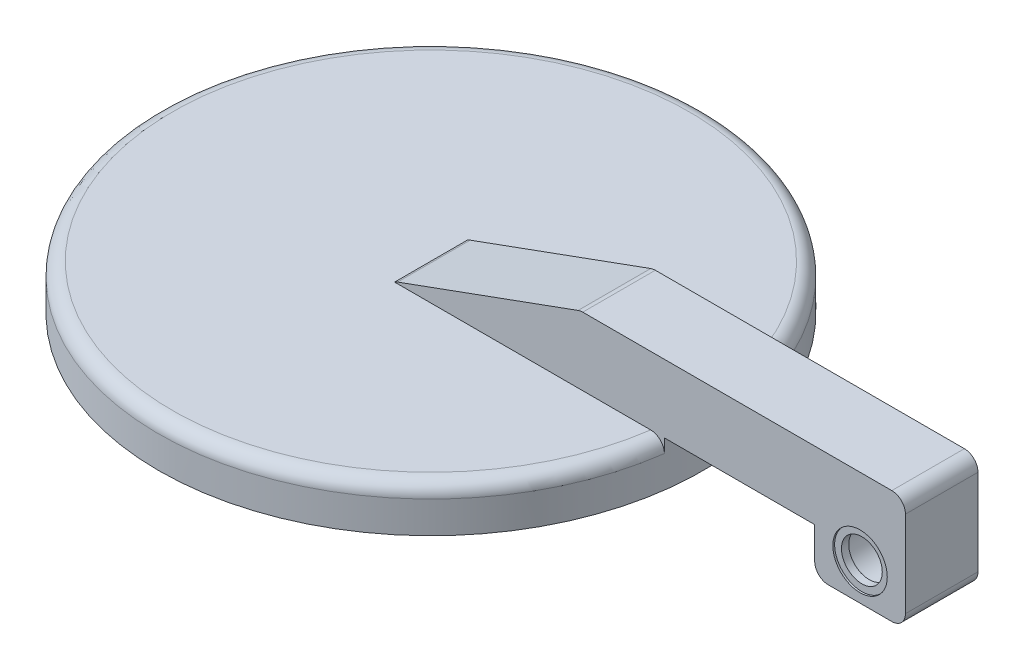
SolidWorks part; units mm, degrees
ref_plane "Front Plane" through (0, 0, 0) normal (0, 0, 1) x (1, 0, 0)
ref_plane "Top Plane" through (0, 0, 0) normal (0, 1, 0) x (1, 0, 0)
ref_plane "Right Plane" through (0, 0, 0) normal (1, 0, 0) x (0, 0, -1)
sketch "Sketch2" plane through (0, 0, 0) normal (0, 0, 1) x (1, 0, 0)
  line L7 (0, 0) -> (30, 0)
  line L8 (0, 0) -> (0, 5)
  line L9 (0, 5) -> (30, 5)
  line L10 (30, 0) -> (30, 5)
  dimension "D1" = 5
  dimension "D2" = 30
revolve "Revolve1" add sketch "Sketch2" angle 360 about L8
sketch "Sketch3" plane through (0, 5, 0) normal (0, 1, 0) x (1, 0, 0)
  line L0 (0, -10) -> (0, 10) construction
  line L1 (0, 10) -> (35, 10)
  line L2 (35, 10) -> (35, 6)
  line L3 (35, 6) -> (0, 6)
  line L4 (0, 10) -> (0, 6)
  line L5 (0, -10) -> (35, -10)
  line L6 (35, -10) -> (35, -6)
  line L7 (35, -6) -> (0, -6)
  line L8 (0, -6) -> (0, -10)
  line L9 (0, 4) -> (0, -4)
  line L10 (0, 4) -> (56.3, 4)
  line L11 (0, -4) -> (56.3, -4)
  line L12 (56.3, -4) -> (56.3, 4)
  point P4 (0, 0)
  point P13 (0, 0)
  circle M1 centre (0, 0) radius 30
  dimension "D1" = 20
  dimension "D2" = 35
  dimension "D3" = 4
  dimension "0.7" = 8
  dimension "D5" = 56.3
extrude "Boss-Extrude1" add sketch "Sketch3" along normal blind 7.5 contours L9 L11 L10 M1 | L11 L12 L10 M1 region at (14.9555, 5, 0) region at (43.1053, 5, 0)
sketch "Sketch4" plane through (0, 0, 0) normal (0, 0, 1) x (1, 0, 0)
  line L5 (35, 8.75) -> (37.8, 8.75) construction
  line L7 (56.3, 8.75) -> (37.8, 8.75) construction
  line L8 (56.3, 12.5) -> (56.3, 5) construction
  line L10 (-0.1339, 5) -> (20.4721, 12.5)
  line L11 (29.7321, 5) -> (-30, 5) construction
  line L12 (0, 12.5) -> (56.3, 12.5) construction
  line L13 (0, 5) -> (29.7321, 5) construction
  line L14 (20.4721, 12.5) -> (0, 12.5)
  line L15 (0, 12.5) -> (-0.1339, 5)
  circle A0 centre (37.8, 8.75) radius 2
  dimension "D3" = 4
  dimension "D1" = 20
  dimension "D2" = 18.5
extrude "Cut-Extrude1" cut sketch "Sketch4" against normal mid plane 30 contours L14 L15 L10
sketch "Sketch6" plane through (0, 5, 0) normal (0, -1, 0) x (1, 0, 0)
  line L6 (56.3, 4) -> (46.3, 4)
  line L7 (56.3, 4) -> (56.3, -4) construction
  line L8 (29.7321, 4) -> (56.3, 4) construction
  line L9 (46.3, 4) -> (46.3, -4)
  line L10 (29.7321, -4) -> (56.3, -4) construction
  line L11 (46.3, -4) -> (56.3, -4)
  line L12 (56.3, -4) -> (56.3, 4)
  dimension "D1" = 10
extrude "Boss-Extrude2" add sketch "Sketch6" along normal blind 5
sketch "Sketch7" plane through (0, 0, 4) normal (0, 0, 1) x (1, 0, 0)
  line L0 (51.3, 4) -> (51.3, 0) construction
  line L2 (56.3, 0) -> (46.3, 0) construction
  circle A0 centre (51.3, 4) radius 3
  dimension "D2" = 6
  dimension "D1" = 4
extrude "Cut-Extrude2" cut sketch "Sketch7" against normal blind 10
fillet "Fillet2" radius 1.5 6 edges at (46.3, 0, 0) (56.3, 0, 0) (56.3, 12.5, 0) (20.4721, 12.5, 0) (0, 5.0487, 0) (-30, 5, 0)
sketch "Sketch9" plane through (0, 0, -4) normal (0, 0, -1) x (-1, 0, 0)
  circle A0 centre (-51.3, 4) radius 3
  circle A1 centre (-51.3, 4) radius 4
  dimension "D1" = 6
  dimension "D2" = 8
sketch "Sketch10" plane through (0, 0, 4) normal (0, 0, 1) x (1, 0, 0)
  circle A0 centre (51.3, 4) radius 3
  circle A1 centre (51.3, 4) radius 2.25
  dimension "D1" = 6
  dimension "D2" = 4.5
extrude "Boss-Extrude4" add sketch "Sketch10" along normal blind 0.8 from offset 1 offset against normal yes
